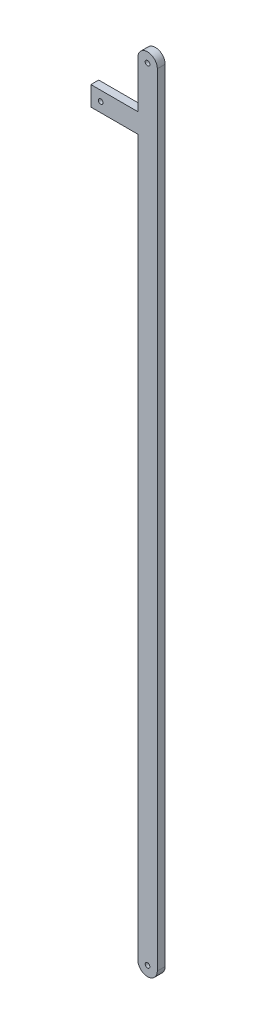
SolidWorks part; units mm, degrees
ref_plane "Front Plane" through (0, 0, 0) normal (0, 0, 1) x (1, 0, 0)
ref_plane "Top Plane" through (0, 0, 0) normal (0, 1, 0) x (1, 0, 0)
ref_plane "Right Plane" through (0, 0, 0) normal (1, 0, 0) x (0, 0, -1)
sketch "Sketch1" plane through (0, 0, 0) normal (0, 0, 1) x (1, 0, 0)
  line L0 (-12.5, 0) -> (-12.5, -60)
  line L1 (12.5, 0) -> (12.5, -1000)
  line L2 (-12.5, -500) -> (12.5, -500) construction
  line L4 (-72.5, -60) -> (-72.5, -85)
  line L5 (-72.5, -85) -> (-12.5, -85)
  line L6 (-12.5, 0) -> (12.5, 0) construction
  line L7 (-12.5, -85) -> (-12.5, -1000)
  line L8 (-72.5, -60) -> (-47.5, -60) construction
  line L9 (-60, -60) -> (-60, -85) construction
  line L10 (-72.5, -60) -> (-12.5, -60)
  circle A0 centre (0, 0) radius 3
  arc A1 (12.5, 0) -> (-12.5, 0) centre (0, 0) ccw
  arc A2 (12.5, -1000) -> (-12.5, -1000) centre (0, -1000) cw
  circle A3 centre (0, -1000) radius 3
  circle A4 centre (-60, -72.5) radius 3
  dimension "D1" = 6
  dimension "D2" = 25
  dimension "D6" = 6
  dimension "D3" = 1000
  dimension "D4" = 72.5
  dimension "D5" = 60
extrude "Boss-Extrude1" add sketch "Sketch1" along normal blind 10
